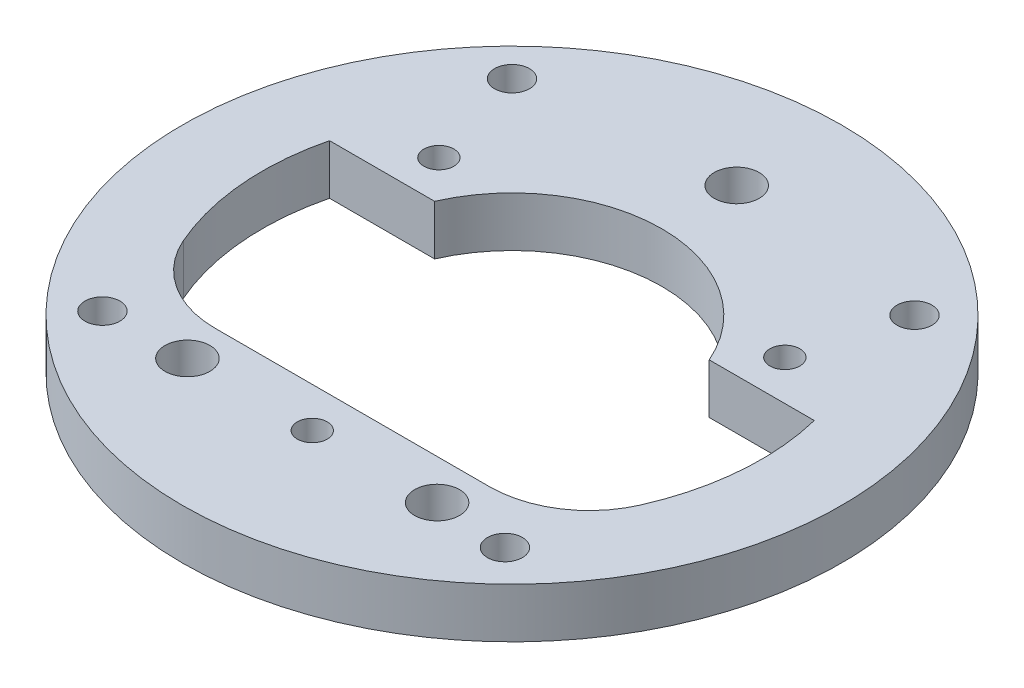
SolidWorks part; units mm, degrees
ref_plane "Front Plane" through (0, 0, 0) normal (0, 0, 1) x (1, 0, 0)
ref_plane "Top Plane" through (0, 0, 0) normal (0, 1, 0) x (1, 0, 0)
ref_plane "Right Plane" through (0, 0, 0) normal (1, 0, 0) x (0, 0, -1)
sketch "Sketch1" plane through (0, 0, 0) normal (0, 1, 0) x (1, 0, 0)
  circle A0 centre (0, 0) radius 33
  circle A1 centre (0, 0) radius 25
  dimension "D1" = 66
  dimension "D2" = 8
extrude "Boss-Extrude1" add sketch "Sketch1" along normal blind 5
sketch "Sketch2" plane through (0, 5, 0) normal (0, 1, 0) x (1, 0, 0)
  line L0 (-19.2094, -16) -> (19.2094, -16)
  line L1 (-24.2693, 6) -> (-13.7477, 6)
  line L2 (0, 0) -> (7.7557, 0) construction
  line L3 (13.7477, 6) -> (24.2693, 6)
  line L4 (-20.5061, 20.5061) -> (0, 0) construction
  circle A0 centre (0, 22.5) radius 2.25 construction
  circle A1 centre (-12.5, -20) radius 2.25 construction
  circle A2 centre (12.5, -20) radius 2.25 construction
  circle A3 centre (0, -20) radius 1.5 construction
  circle A4 centre (0, 0) radius 20 construction
  circle A5 centre (-17.3205, 10) radius 1.5 construction
  circle A6 centre (0, 0) radius 25 construction
  circle A7 centre (17.3205, 10) radius 1.5 construction
  arc A8 (-13.7477, 6) -> (13.7477, 6) centre (0, 0) cw
  arc A9 (24.2693, 6) -> (-24.2882, 5.9232) centre (0, 0) ccw
  arc A10 (19.2094, -16) -> (-19.2094, -16) centre (0, 0) cw
  circle A12 centre (0, 0) radius 29 construction
  circle A13 centre (0, 0) radius 33 construction
  circle A14 centre (-20.5061, 20.5061) radius 1.75 construction
  circle A15 centre (20.1525, 20.1525) radius 1.75 construction
  circle A16 centre (19.799, -20.5061) radius 1.75 construction
  circle A17 centre (-20.8597, -20.1525) radius 1.75 construction
  point P19 (0, 0)
  point P44 (-0.3536, 0)
  circle M2 centre (0, 0) radius 25
  dimension "D5" = 4.5
  dimension "D6" = 4.5
  dimension "D7" = 4.5
  dimension "D10" = 3
  dimension "D12" = 15
  dimension "D16" = 3.5
  dimension "D1" = 25
  dimension "D2" = 12.5
  dimension "D3" = 22.5
  dimension "D4" = 20
  dimension "D9" = 5
  dimension "D11" = 4
  dimension "D13" = 4
  dimension "D14" = 4
  dimension "D15" = 135
  dimension "D8" = 3
  dimension "D17" = 4
extrude "Saliente-Extruir1" add sketch "Sketch2" against normal up to surface (5 mm away) contours L1 A8 L3 M2 | L0 M2 region at (0, 5, 19.6621) region at (0, 5, -15.401) up to face at (0, 0, 33)
sketch "Croquis1" plane through (0, 5, 0) normal (0, 1, 0) x (1, 0, 0)
  circle A0 centre (-20.5061, 20.5061) radius 1.75 construction
  circle A1 centre (-20.5061, 20.5061) radius 1.75
  circle A2 centre (0, 22.5) radius 2.25 construction
  circle A3 centre (0, 22.5) radius 2.25
  circle A4 centre (20.1525, 20.1525) radius 1.75 construction
  circle A5 centre (20.1525, 20.1525) radius 1.75
  circle A6 centre (-17.3205, 10) radius 1.5 construction
  circle A7 centre (-17.3205, 10) radius 1.5
  circle A8 centre (17.3205, 10) radius 1.5 construction
  circle A9 centre (17.3205, 10) radius 1.5
  circle A10 centre (0, -20) radius 1.5 construction
  circle A11 centre (0, -20) radius 1.5
  circle A12 centre (12.5, -20) radius 2.25 construction
  circle A13 centre (12.5, -20) radius 2.25
  circle A14 centre (-12.5, -20) radius 2.25 construction
  circle A15 centre (-12.5, -20) radius 2.25
  circle A16 centre (-20.8597, -20.1525) radius 1.75 construction
  circle A17 centre (-20.8597, -20.1525) radius 1.75
  circle A18 centre (19.799, -20.5061) radius 1.75 construction
  circle A19 centre (19.799, -20.5061) radius 1.75
extrude "Cortar-Extruir1" cut sketch "Croquis1" against normal up to next
fillet "Redondeo1" radius 10 2 edges at (19.2094, 2.5, 16) (-19.2094, 2.5, 16)
equation "\"D2@Sketch2\"=\"D1@Sketch2\"/2"
equation "\"D6@Sketch2\"=\"D5@Sketch2\""
equation "\"D7@Sketch2\"=\"D6@Sketch2\""
equation "\"D10@Sketch2\"=\"D8@Sketch2\""
